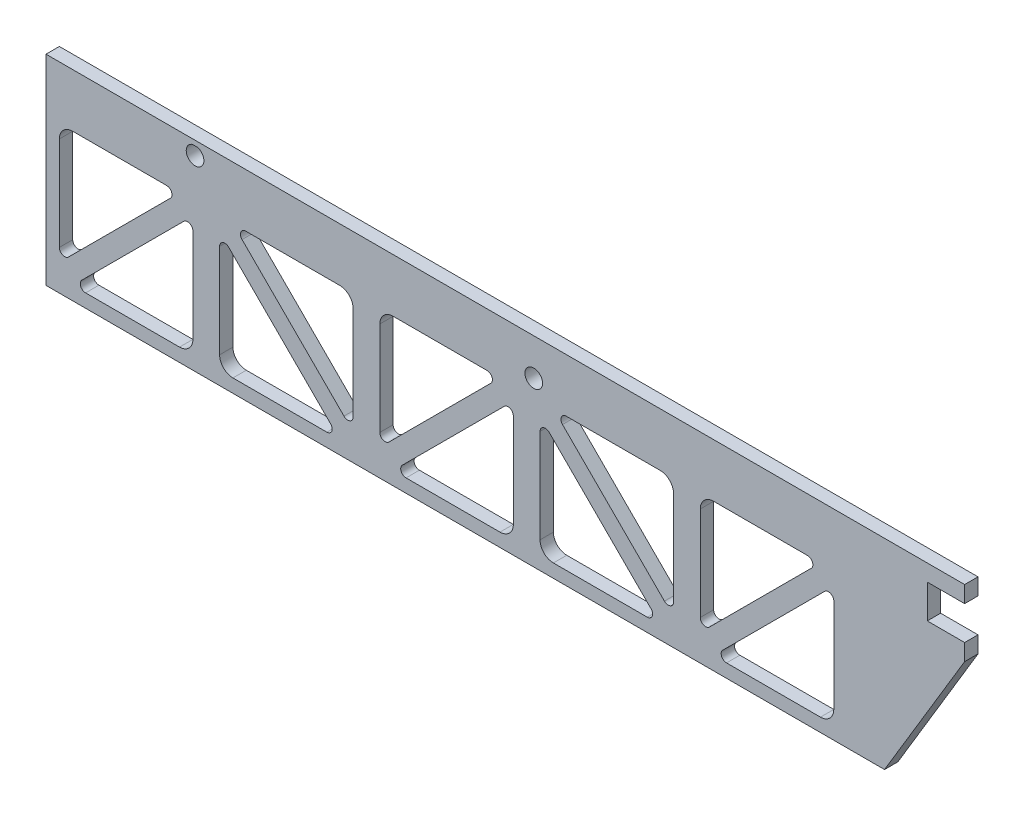
SolidWorks part; units mm, degrees
material "Balsa"
ref_plane "Front Plane" through (0, 0, 0) normal (0, 0, 1) x (1, 0, 0)
ref_plane "Top Plane" through (0, 0, 0) normal (0, 1, 0) x (1, 0, 0)
ref_plane "Right Plane" through (0, 0, 0) normal (1, 0, 0) x (0, 0, -1)
sketch "Model" plane through (0, 0, 0) normal (0, 0, 1) x (1, 0, 0)
  line L0 (74.8917, 92.9005) -> (74.8917, 84.8995)
  line L1 (74.8917, 84.8995) -> (66.8907, 84.8995)
  line L2 (66.8907, 84.8995) -> (66.8907, 92.9005)
  line L3 (66.8907, 92.9005) -> (74.8917, 92.9005)
  line L4 (235.8537, 81.866) -> (235.9382, 73.8654)
  line L5 (235.9382, 73.8654) -> (227.9376, 73.7809)
  line L6 (227.9376, 73.7809) -> (227.8532, 81.7815)
  line L7 (227.8532, 81.7815) -> (235.8537, 81.866)
  line L8 (171.2321, 6.35) -> (215.9, 6.35)
  line L9 (217.9139, 59.1639) -> (169.4361, 10.6861)
  line L10 (222.25, 57.3679) -> (222.25, 12.7)
  line L11 (234.95, 57.3679) -> (234.95, 12.7)
  line L12 (239.2861, 59.1639) -> (287.7639, 10.6861)
  line L13 (241.3, 6.35) -> (285.9679, 6.35)
  line L14 (294.1139, 17.0361) -> (245.6361, 65.5139)
  line L15 (247.4321, 69.85) -> (292.1, 69.85)
  line L16 (298.45, 63.5) -> (298.45, 18.8321)
  line L17 (323.6321, 6.35) -> (368.3, 6.35)
  line L18 (370.3139, 59.1639) -> (321.8361, 10.6861)
  line L19 (374.65, 57.3679) -> (374.65, 12.7)
  line L20 (18.8321, 6.35) -> (63.5, 6.35)
  line L21 (17.0361, 10.6861) -> (65.5139, 59.1639)
  line L22 (69.85, 57.3679) -> (69.85, 12.7)
  line L23 (82.55, 57.3679) -> (82.55, 12.7)
  line L24 (86.8861, 59.1639) -> (135.3639, 10.6861)
  line L25 (88.9, 6.35) -> (133.5679, 6.35)
  line L26 (93.2361, 65.5139) -> (141.7139, 17.0361)
  line L27 (95.0321, 69.85) -> (139.7, 69.85)
  line L28 (146.05, 63.5) -> (146.05, 18.8321)
  line L29 (163.0861, 17.0361) -> (211.5639, 65.5139)
  line L30 (158.75, 63.5) -> (158.75, 18.8321)
  line L31 (165.1, 69.85) -> (209.7679, 69.85)
  line L32 (315.4861, 17.0361) -> (363.9639, 65.5139)
  line L33 (311.15, 63.5) -> (311.15, 18.8321)
  line L34 (317.5, 69.85) -> (362.1679, 69.85)
  line L35 (419.1, 87.376) -> (419.1, 71.374)
  line L36 (436.88, 87.376) -> (419.1, 87.376)
  line L37 (436.88, 87.376) -> (436.88, 95.25)
  line L38 (0, 95.25) -> (436.88, 95.25)
  line L39 (0, 0) -> (0, 95.25)
  line L40 (0, 0) -> (398.78, 0)
  line L41 (436.88, 63.5) -> (398.78, 0)
  line L42 (436.88, 63.5) -> (436.88, 71.374)
  line L43 (419.1, 71.374) -> (436.88, 71.374)
  line L44 (6.35, 63.5) -> (6.35, 18.8321)
  line L45 (12.7, 69.85) -> (57.3679, 69.85)
  line L46 (59.1639, 65.5139) -> (10.6861, 17.0361)
  arc A0 (215.9, 6.35) -> (222.25, 12.7) centre (215.9, 12.7) ccw
  arc A1 (169.4361, 10.6861) -> (171.2321, 6.35) centre (171.2321, 8.89) ccw
  arc A2 (222.25, 57.3679) -> (217.9139, 59.1639) centre (219.71, 57.3679) ccw
  arc A3 (239.2861, 59.1639) -> (234.95, 57.3679) centre (237.49, 57.3679) ccw
  arc A4 (285.9679, 6.35) -> (287.7639, 10.6861) centre (285.9679, 8.89) ccw
  arc A5 (234.95, 12.7) -> (241.3, 6.35) centre (241.3, 12.7) ccw
  arc A6 (247.4321, 69.85) -> (245.6361, 65.5139) centre (247.4321, 67.31) ccw
  arc A7 (298.45, 63.5) -> (292.1, 69.85) centre (292.1, 63.5) ccw
  arc A8 (294.1139, 17.0361) -> (298.45, 18.8321) centre (295.91, 18.8321) ccw
  arc A9 (321.8361, 10.6861) -> (323.6321, 6.35) centre (323.6321, 8.89) ccw
  arc A10 (374.65, 57.3679) -> (370.3139, 59.1639) centre (372.11, 57.3679) ccw
  arc A11 (368.3, 6.35) -> (374.65, 12.7) centre (368.3, 12.7) ccw
  arc A12 (63.5, 6.35) -> (69.85, 12.7) centre (63.5, 12.7) ccw
  arc A13 (17.0361, 10.6861) -> (18.8321, 6.35) centre (18.8321, 8.89) ccw
  arc A14 (69.85, 57.3679) -> (65.5139, 59.1639) centre (67.31, 57.3679) ccw
  arc A15 (86.8861, 59.1639) -> (82.55, 57.3679) centre (85.09, 57.3679) ccw
  arc A16 (133.5679, 6.35) -> (135.3639, 10.6861) centre (133.5679, 8.89) ccw
  arc A17 (82.55, 12.7) -> (88.9, 6.35) centre (88.9, 12.7) ccw
  arc A18 (95.0321, 69.85) -> (93.2361, 65.5139) centre (95.0321, 67.31) ccw
  arc A19 (146.05, 63.5) -> (139.7, 69.85) centre (139.7, 63.5) ccw
  arc A20 (141.7139, 17.0361) -> (146.05, 18.8321) centre (143.51, 18.8321) ccw
  arc A21 (158.75, 18.8321) -> (163.0861, 17.0361) centre (161.29, 18.8321) ccw
  arc A22 (165.1, 69.85) -> (158.75, 63.5) centre (165.1, 63.5) ccw
  arc A23 (211.5639, 65.5139) -> (209.7679, 69.85) centre (209.7679, 67.31) ccw
  arc A24 (363.9639, 65.5139) -> (362.1679, 69.85) centre (362.1679, 67.31) ccw
  arc A25 (311.15, 18.8321) -> (315.4861, 17.0361) centre (313.69, 18.8321) ccw
  arc A26 (317.5, 69.85) -> (311.15, 63.5) centre (317.5, 63.5) ccw
  arc A27 (6.35, 18.8321) -> (10.6861, 17.0361) centre (8.89, 18.8321) ccw
  arc A28 (12.7, 69.85) -> (6.35, 63.5) centre (12.7, 63.5) ccw
  arc A29 (59.1639, 65.5139) -> (57.3679, 69.85) centre (57.3679, 67.31) ccw
  dimension "D1" = 95.25
extrude "Boss-Extrude2" add sketch "Model" along normal blind 6.35
sketch "Sketch1" plane through (0, 0, 6.35) normal (0, 0, 1) x (1, 0, 0)
  line L0 (66.8907, 92.9005) -> (66.8907, 84.8995) construction
  line L1 (74.8917, 92.9005) -> (66.8907, 92.9005) construction
  line L2 (74.8917, 92.9005) -> (66.8907, 92.9005)
  line L3 (227.8532, 81.7815) -> (227.9376, 73.7809) construction
  line L4 (66.6875, 93.1037) -> (75.0949, 93.1037)
  line L5 (66.6875, 93.1037) -> (66.6875, 84.6963)
  line L6 (66.6875, 84.6963) -> (75.0949, 84.6963)
  line L7 (75.0949, 93.1037) -> (75.0949, 84.6963)
  line L8 (227.7688, 81.9516) -> (236.1508, 81.9516)
  line L9 (227.7688, 81.9516) -> (227.7688, 73.5696)
  line L10 (227.7688, 73.5696) -> (236.1508, 73.5696)
  line L11 (236.1508, 81.9516) -> (236.1508, 73.5696)
  line L13 (235.8537, 81.866) -> (227.8532, 81.7815) construction
  circle A0 centre (70.8912, 88.9) radius 4.2037
  circle A1 centre (231.9598, 77.7606) radius 4.191
  point P10 (0, 0)
  point P18 (232.4875, 77.5563)
  point P22 (231.8534, 75.3757)
  dimension "D1" = 8.4074
  dimension "D5" = 8.382
  dimension "D2" = 4.0005
  dimension "D3" = 8.001
  dimension "D4" = 4.0005
  dimension "D6" = 4.064
  dimension "D7" = 4.064
extrude "Boss-Extrude3" add sketch "Sketch1" against normal up to surface (6.35 mm away) contours A0 L4 L5 | A0 L7 L4 | A0 L6 L7 | A0 L5 L6 | A1 L9 L10 | A1 L8 L9 | A1 L11 L8 | A1 L10 L11 region at (74.1559, 92.1647, 6.35) region at (67.6265, 92.1647, 6.35) region at (74.1559, 85.6353, 6.35) region at (67.6265, 85.6353, 6.35) region at (228.705, 81.0155, 6.35) region at (235.2147, 81.0155, 6.35) region at (228.705, 74.5058, 6.35) region at (235.2147, 74.5058, 6.35) up to face at (70.8912, 88.9, 0)
extrude "Cut-Extrude1" cut sketch "Sketch1<3>" against normal up to surface (6.35 mm away) contours A0 L2 | A1 region at (70.8912, 88.874, 6.35) region at (231.9598, 77.7606, 6.35) up to face at (231.9052, 77.8141, 0)
sketch "Sketch1<3>" plane through (0, 0, 6.35) normal (0, 0, 1) x (1, 0, 0) same geometry as "Sketch1"
equation "\"D4@Sketch1\"=\"D3@Sketch1\"/2"
equation "\"D6@Sketch1\"=.16"
